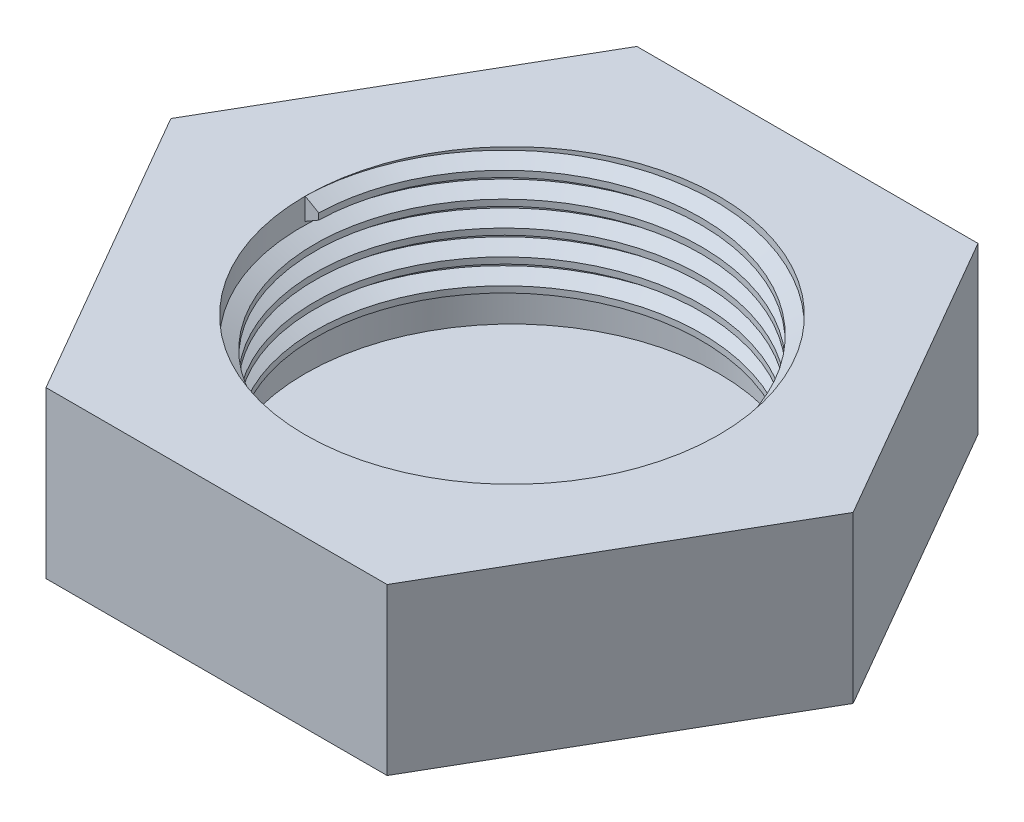
SolidWorks part; units mm, degrees
ref_plane "Alzado" through (0, 0, 0) normal (0, 0, 1) x (1, 0, 0)
ref_plane "Planta" through (0, 0, 0) normal (0, 1, 0) x (1, 0, 0)
ref_plane "Vista lateral" through (0, 0, 0) normal (1, 0, 0) x (0, 0, -1)
sketch "Croquis1" plane through (0, 0, 0) normal (0, 1, 0) x (1, 0, 0)
  line L1 (-28.8675, 0) -> (-14.4338, -25)
  line L2 (-14.4338, -25) -> (14.4338, -25)
  line L3 (14.4338, -25) -> (28.8675, 0)
  line L4 (28.8675, 0) -> (14.4338, 25)
  line L5 (14.4338, 25) -> (-14.4338, 25)
  line L6 (-14.4338, 25) -> (-28.8675, 0)
  circle A0 centre (0, 0) radius 25 construction
  dimension "D1" = 50
extrude "Saliente-Extruir1" add sketch "Croquis1" along normal blind 10
sketch "Croquis2" plane through (0, 10, 0) normal (0, 1, 0) x (1, 0, 0)
  circle A0 centre (0, 0) radius 17.5
  dimension "D1" = 35
extrude "Cortar-Extruir1" cut sketch "Croquis2" against normal blind 10
thread "Rosca1" pitch 2.1167 method extrude profile "Perfil de rosca1" start angle 0, offset 0, length 10, pitch 2.1167, diameter 35
ref_plane "Plano1" through (-17.5, 10, 0) normal (0, 0, 1) x (-1, 0, 0)
sketch "Perfil de rosca1" plane through (-17.5, 10, 0) normal (0, 0, 1) x (-1, 0, 0)
  line L0 (0, 0) -> (0, 2.1167) construction
  line L11 (0, 0) -> (0, 1.8521)
  line L12 (0, 1.8521) -> (-1.1457, 1.1906)
  line L13 (-1.1457, 1.1906) -> (-1.1457, 0.6615)
  line L15 (-1.1457, 0.6615) -> (0, 0)
  line L17 (-1.1457, 0.926) -> (0, 0.926) construction
  point P2 (0, 0)
  dimension "Pitch" = 2.1167
  dimension "Profile_Angle" = 60
  dimension "Profile_Land" = 0.5292
  dimension "Profile_Height" = 1.1457
sketch "Croquis5" plane through (0, 0, 0) normal (0, -1, 0) x (1, 0, 0)
  line L1 (-28.8675, 0) -> (-14.4338, -25)
  line L2 (-14.4338, -25) -> (14.4338, -25)
  line L3 (14.4338, -25) -> (28.8675, 0)
  line L4 (28.8675, 0) -> (14.4338, 25)
  line L5 (14.4338, 25) -> (-14.4338, 25)
  line L6 (-14.4338, 25) -> (-28.8675, 0)
  circle A0 centre (0, 0) radius 25 construction
  circle A1 centre (0, 0) radius 17.5
  dimension "D1" = 35
extrude "Saliente-Extruir4" add sketch "Croquis5" along normal blind 3
sketch "Croquis6" plane through (0, -3, 0) normal (0, -1, 0) x (1, 0, 0)
  line L1 (-28.8675, 0) -> (-14.4338, -25)
  line L2 (-14.4338, -25) -> (14.4338, -25)
  line L3 (14.4338, -25) -> (28.8675, 0)
  line L4 (28.8675, 0) -> (14.4338, 25)
  line L5 (14.4338, 25) -> (-14.4338, 25)
  line L6 (-14.4338, 25) -> (-28.8675, 0)
  circle A0 centre (0, 0) radius 25 construction
extrude "Saliente-Extruir5" add sketch "Croquis6" along normal blind 1
